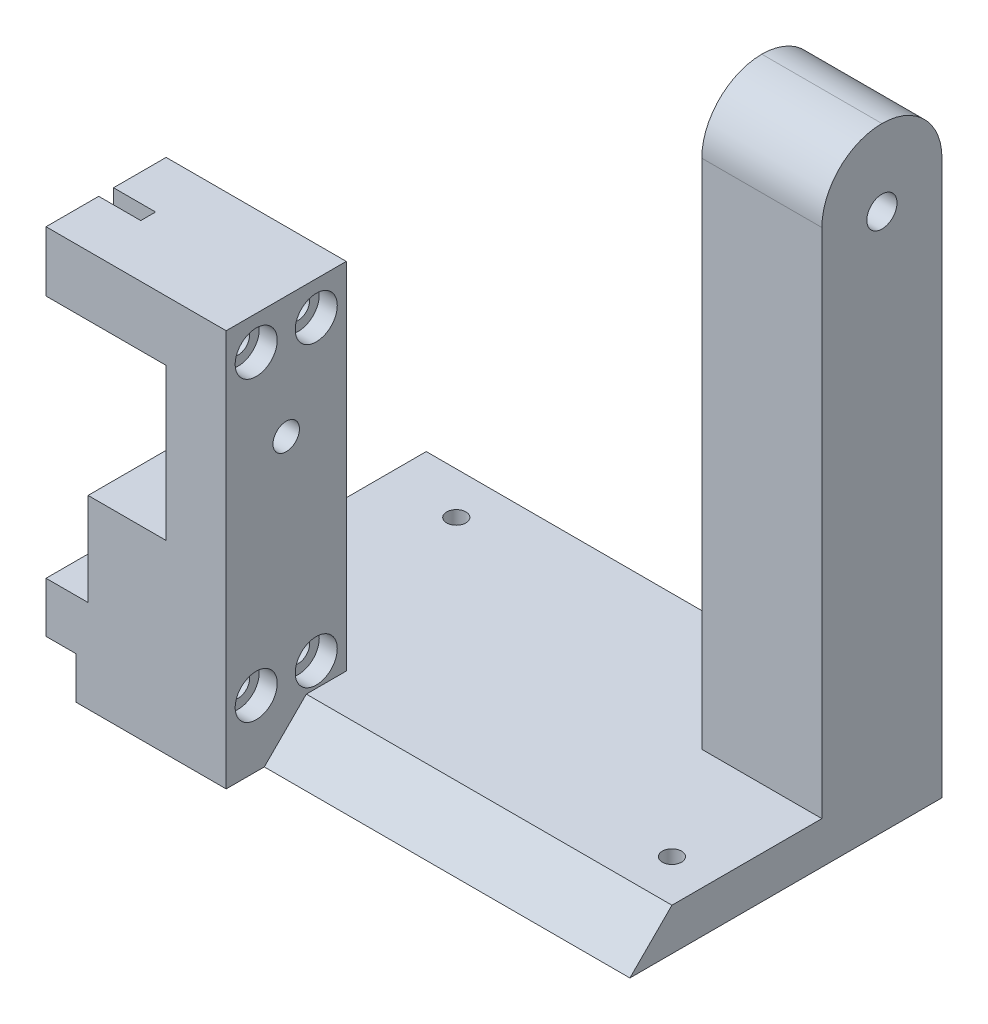
SolidWorks part; units mm, degrees
ref_plane "Front Plane" through (0, 0, 0) normal (0, 0, 1) x (1, 0, 0)
ref_plane "Top Plane" through (0, 0, 0) normal (0, 1, 0) x (1, 0, 0)
ref_plane "Right Plane" through (0, 0, 0) normal (1, 0, 0) x (0, 0, -1)
sketch "Sketch1" plane through (0, 0, 0) normal (0, 1, 0) x (1, 0, 0)
  line L1 (-12.5, -10) -> (12.5, -10)
  line L2 (-12.5, -10) -> (-12.5, 10)
  line L3 (-12.5, 10) -> (12.5, 10)
  line L4 (12.5, -10) -> (12.5, 10)
  line L5 (-12.5, -10) -> (12.5, 10) construction
  line L6 (-12.5, 10) -> (12.5, -10) construction
  line L7 (53.3814, 28.32) -> (73.3814, 28.32)
  line L8 (53.3814, 28.32) -> (53.3814, 48.32)
  line L9 (53.3814, 48.32) -> (73.3814, 48.32)
  line L10 (73.3814, 28.32) -> (73.3814, 48.32)
  line L11 (53.3814, 28.32) -> (73.3814, 48.32) construction
  line L12 (53.3814, 48.32) -> (73.3814, 28.32) construction
  point P0 (0, 0)
  point P1 (63.3814, 38.32)
  point P2 (0, 0)
  point P8 (63.3814, 38.32)
  dimension "D1" = 40.8814
  dimension "D2" = 38.32
  dimension "D3" = 20
  dimension "D4" = 20
  dimension "D5" = 25
  dimension "D6" = 20
extrude "Boss-Extrude1" add sketch "Sketch1" along normal blind 168.81
sketch "Sketch2" plane through (0, 0, 10) normal (0, 0, 1) x (1, 0, 0)
  line L0 (12.5, 168.81) -> (12.5, 0) construction
  line L1 (-12.5, 168.81) -> (12.5, 168.81)
  line L2 (-12.5, 168.81) -> (-12.5, 124.102)
  line L3 (-12.5, 124.102) -> (12.5, 124.102)
  line L4 (12.5, 168.81) -> (12.5, 124.102)
  dimension "D1" = 44.708
extrude "Cut-Extrude1" cut sketch "Sketch2" against normal through all both and the other way through all
fillet "Fillet2" radius 10 2 edges at (63.3814, 168.81, -48.32) (63.3814, 168.81, -28.32)
sketch "Sketch3" plane through (12.5, 0, 0) normal (1, 0, 0) x (0, 0, -1)
  line L0 (-10, 124.102) -> (-10, 0) construction
  line L1 (-10, 0) -> (10, 0) construction
  circle A0 centre (0, 112.395) radius 2.2
  dimension "D1" = 4.4
  dimension "D2" = 10
  dimension "D3" = 112.395
sketch "Sketch4" plane through (73.3814, 0, 0) normal (1, 0, 0) x (0, 0, -1)
  line L1 (28.32, 158.81) -> (28.32, 0) construction
  line L2 (28.32, 0) -> (48.32, 0) construction
  circle A0 centre (38.32, 156.1084) radius 2.515
  dimension "D1" = 5.03
  dimension "D2" = 10
  dimension "D3" = 156.1084
extrude "Cut-Extrude2" cut sketch "Sketch4" against normal through all both
extrude "Cut-Extrude3" cut sketch "Sketch3" against normal through all both
sketch "Sketch5" plane through (12.5, 0, 0) normal (1, 0, 0) x (0, 0, -1)
  line L0 (48.32, 158.81) -> (48.32, 0) construction
  line L1 (-10, 0) -> (48.32, 0)
  line L2 (-10, 0) -> (-10, 66.56)
  line L3 (-10, 66.56) -> (48.32, 66.56)
  line L4 (48.32, 0) -> (48.32, 66.56)
  dimension "D1" = 66.56
extrude "Cut-Extrude4" cut sketch "Sketch5" against normal mid plane 168.81
sketch "Sketch6" plane through (0, 66.56, 0) normal (0, -1, 0) x (1, 0, 0)
  line L0 (12.5, 10) -> (12.5, -10) construction
  line L1 (-12.5, 10) -> (73.3814, 10)
  line L2 (-12.5, 10) -> (-12.5, -48.32)
  line L3 (-12.5, -48.32) -> (73.3814, -48.32)
  line L4 (73.3814, 10) -> (73.3814, -48.32)
  line L9 (73.3814, 10) -> (12.5, 10)
  line L10 (73.3814, 10) -> (73.3814, 3.65)
  line L11 (73.3814, 3.65) -> (12.5, 3.65)
  line L12 (12.5, 10) -> (12.5, 3.65)
  line M5 (73.3814, -28.32) -> (53.3814, -28.32)
  line M6 (53.3814, -28.32) -> (53.3814, -48.32)
  dimension "D1" = 6.35
extrude "Boss-Extrude2" add sketch "Sketch6" against normal blind 7 contours L12 L1 L2 L3 L4 L11 M6 M5
chamfer "Chamfer1" distance 7 angle 45 1 edges at (42.9407, 73.56, 3.65)
sketch "Sketch8" plane through (-12.5, 0, 0) normal (-1, 0, 0) x (0, 0, 1)
  line L0 (-10, 124.102) -> (-10, 73.56) construction
  line L1 (-10, 112.395) -> (10, 112.395)
  line L2 (-10, 112.395) -> (-10, 81.945)
  line L3 (-10, 81.945) -> (10, 81.945)
  line L4 (10, 112.395) -> (10, 81.945)
  line L5 (10, 124.102) -> (10, 66.56) construction
  line L7 (-10, 112.395) -> (10, 112.395)
  line L8 (-10, 112.395) -> (-10, 126.2538)
  line L9 (-10, 126.2538) -> (10, 126.2538)
  line L10 (10, 112.395) -> (10, 126.2538)
  point P12 (0, 112.395)
  dimension "D1" = 30.45
extrude "Cut-Extrude6" cut sketch "Sketch8" against normal blind 2
sketch "Sketch9" plane through (-10.5, 0, 0) normal (-1, 0, 0) x (0, 0, 1)
  line L0 (10, 81.945) -> (10, 124.102) construction
  line L1 (-10, 129.2422) -> (10, 129.2422)
  line L2 (-10, 129.2422) -> (-10, 97.395)
  line L3 (-10, 97.395) -> (10, 97.395)
  line L4 (10, 129.2422) -> (10, 97.395)
  circle A0 centre (0, 112.395) radius 2.2 construction
  dimension "D1" = 15
extrude "Cut-Extrude7" cut sketch "Sketch9" against normal blind 13
sketch "Sketch10" plane through (2.5, 0, 0) normal (-1, 0, 0) x (0, 0, 1)
  line L0 (-10, 124.102) -> (-10, 97.395) construction
  line L1 (-10, 122.645) -> (10, 122.645)
  line L2 (-10, 122.645) -> (-10, 132.645)
  line L3 (-10, 132.645) -> (10, 132.645)
  line L4 (10, 122.645) -> (10, 132.645)
  line L5 (10, 97.395) -> (10, 124.102) construction
  line L6 (-10, 81.945) -> (10, 81.945) construction
  dimension "D1" = 40.7
  dimension "D2" = 10
extrude "Boss-Extrude3" add sketch "Sketch10" along normal up to surface and the other way up to surface
sketch "Sketch11" plane through (-12.5, 0, 0) normal (-1, 0, 0) x (0, 0, 1)
  line L0 (-10, 81.945) -> (-10, 73.56) construction
  line L1 (10, 81.945) -> (-10, 81.945)
  line L2 (10, 81.945) -> (10, 73.56)
  line L3 (10, 73.56) -> (-10, 73.56)
  line L4 (-10, 81.945) -> (-10, 73.56)
  line L6 (10, 81.945) -> (10, 66.56) construction
  line L8 (-10, 73.56) -> (-48.32, 73.56) construction
extrude "Boss-Extrude4" add sketch "Sketch11" along normal up to surface (5 mm away)
sketch "Sketch12" plane through (0, 66.56, 0) normal (0, -1, 0) x (1, 0, 0)
  circle A0 centre (-0.5, -41.32) radius 1.6
  circle A1 centre (46.3814, -41.32) radius 1.6
  circle A2 centre (66.3814, -10.35) radius 1.6
  circle A3 centre (-0.5, -17) radius 1.6
extrude "Cut-Extrude8" cut sketch "Sketch12" against normal through all both and the other way through all contours A3 | A1 | A2 | A0
sketch "Sketch13" plane through (-17.5, 0, 0) normal (-1, 0, 0) x (0, 0, 1)
  circle A0 centre (-5, 127.045) radius 1.9
  circle A1 centre (5, 127.045) radius 1.9
  circle A2 centre (5, 77.545) radius 1.9
  circle A3 centre (-5, 77.545) radius 1.9
  dimension "D1" = 3.8
  dimension "D2" = 3.8
  dimension "D3" = 3.8
  dimension "D4" = 3.8
extrude "Cut-Extrude11" cut sketch "Sketch13" against normal through all both contours A0 | A1 | A2 | A3
sketch "Sketch14" plane through (12.5, 0, 0) normal (1, 0, 0) x (0, 0, -1)
  circle A0 centre (5, 127.045) radius 3.5
  circle A1 centre (-5, 127.045) radius 3.5
  circle A2 centre (-5, 77.545) radius 3.5
  circle A3 centre (5, 77.545) radius 3.5
  dimension "D1" = 7
  dimension "D2" = 7
  dimension "D3" = 7
  dimension "D4" = 7
extrude "Cut-Extrude12" cut sketch "Sketch14" against normal blind 3
sketch "Sketch16" plane through (-17.5, 0, 0) normal (-1, 0, 0) x (0, 0, 1)
  line L0 (-10, 132.645) -> (10, 132.645) construction
  line L1 (-1.2416, 132.645) -> (1.2273, 132.645)
  line L2 (-1.2416, 132.645) -> (-1.2416, 122.645)
  line L3 (-1.2416, 122.645) -> (1.2273, 122.645)
  line L4 (1.2273, 132.645) -> (1.2273, 122.645)
  line L5 (10, 122.645) -> (-10, 122.645) construction
  line L6 (-10, 81.945) -> (10, 81.945) construction
  line L7 (-1.4576, 81.945) -> (0.8659, 81.945)
  line L8 (-1.4576, 81.945) -> (-1.4576, 73.56)
  line L9 (-1.4576, 73.56) -> (0.8659, 73.56)
  line L10 (0.8659, 81.945) -> (0.8659, 73.56)
  line L11 (10, 73.56) -> (-10, 73.56) construction
extrude "Cut-Extrude13" cut sketch "Sketch16" against normal up to surface (7 mm away) up to face at (-10.5, 89.67, 0)
equation "\"Chassis Height\"= 62.162mm"
